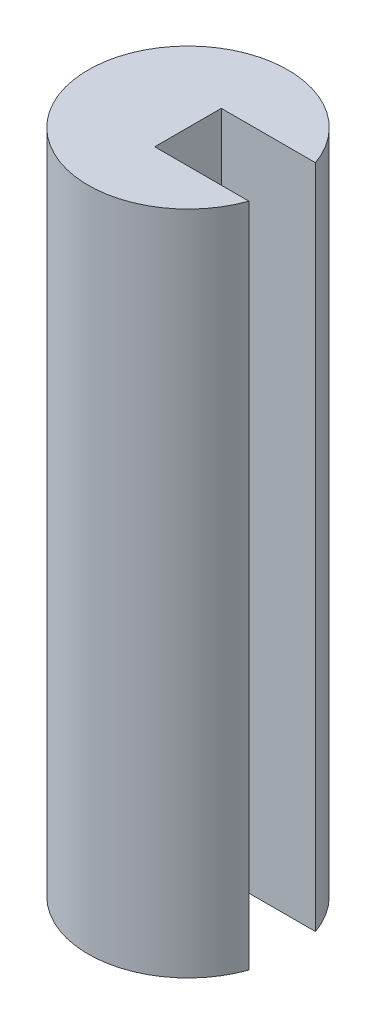
SolidWorks part; units mm, degrees
ref_plane "前视基准面" through (0, 0, 0) normal (0, 0, 1) x (1, 0, 0)
ref_plane "上视基准面" through (0, 0, 0) normal (0, 1, 0) x (1, 0, 0)
ref_plane "右视基准面" through (0, 0, 0) normal (1, 0, 0) x (0, 0, -1)
other "Configuration Table"
sketch "Sketch1" plane through (0, 0, 0) normal (0, 1, 0) x (1, 0, 0)
  circle A0 centre (0, 0) radius 1.5
  dimension "D1" = 3
extrude "Boss-Extrude1" add sketch "Sketch1" along normal blind 10
sketch "Sketch4" plane through (0, 0, 0) normal (0, 0, 1) x (1, 0, 0)
  line L0 (1.5, 0) -> (1.5, 10) construction
  line L1 (1.5, -4.8023) -> (1.5, 17.9247)
  line L2 (-1.5, 10) -> (-1.5, 0) construction
  line L3 (-1.5, 16.2145) -> (-1.5, -2.9719)
sketch "Sketch2" plane through (0, 10, 0) normal (0, 1, 0) x (1, 0, 0)
  line L0 (0, 0) -> (1.5, 0)
  circle A0 centre (0, 0) radius 1.5 construction
extrude "Cut-Extrude-Thin1" cut sketch "Sketch2" against normal through all and the other way through all thin thin type mid plane wall 1
ref_axis "Axis1" through (0, -4.4569, 0) along (0, 1, 0)
ref_axis "Axis2" through (1.5, -4.8023, 0) along (0, 1, 0)
ref_axis "Axis3" through (-1.5, 16.2145, 0) along (0, -1, 0)
